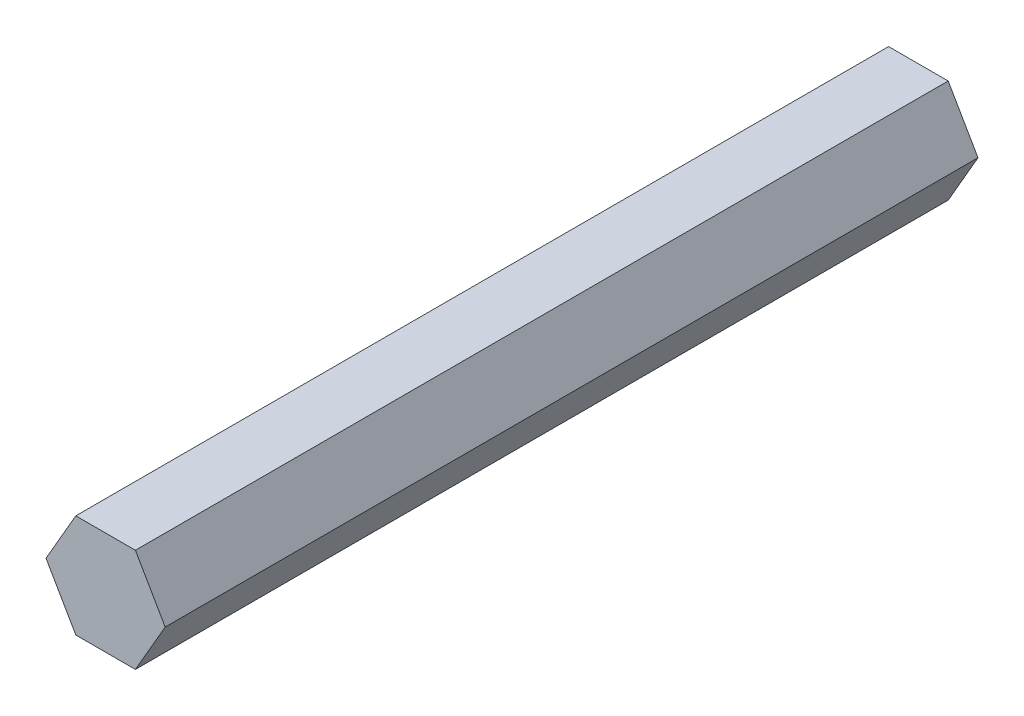
SolidWorks part; units mm, degrees
ref_plane "Front Plane" through (0, 0, 0) normal (0, 0, 1) x (1, 0, 0)
ref_plane "Top Plane" through (0, 0, 0) normal (0, 1, 0) x (1, 0, 0)
ref_plane "Right Plane" through (0, 0, 0) normal (1, 0, 0) x (0, 0, -1)
sketch "Sketch1" plane through (0, 0, 0) normal (0, 0, 1) x (1, 0, 0)
  line L1 (7.3323, 0) -> (3.6662, 6.35)
  line L2 (3.6662, 6.35) -> (-3.6662, 6.35)
  line L3 (-3.6662, 6.35) -> (-7.3323, 0)
  line L4 (-7.3323, 0) -> (-3.6662, -6.35)
  line L5 (-3.6662, -6.35) -> (3.6662, -6.35)
  line L6 (3.6662, -6.35) -> (7.3323, 0)
  circle A0 centre (0, 0) radius 6.35 construction
  dimension "D1" = 12.7
extrude "Boss-Extrude1" add sketch "Sketch1" along normal blind 100
